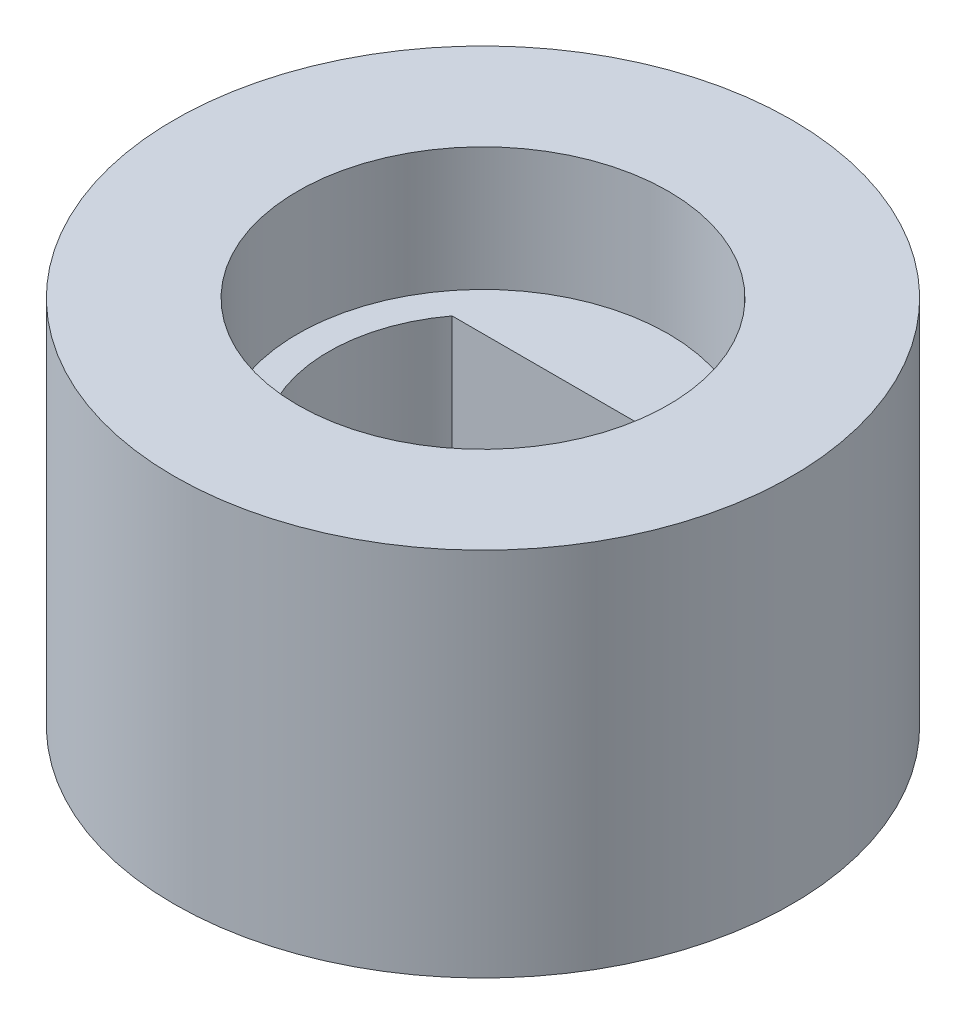
SolidWorks part; units mm, degrees
ref_plane "前视基准面" through (0, 0, 0) normal (0, 0, 1) x (1, 0, 0)
ref_plane "上视基准面" through (0, 0, 0) normal (0, 1, 0) x (1, 0, 0)
ref_plane "右视基准面" through (0, 0, 0) normal (1, 0, 0) x (0, 0, -1)
sketch "草图1" plane through (0, 0, 0) normal (0, 1, 0) x (1, 0, 0)
  line L0 (-2, 1.5) -> (2, 1.5)
  arc A0 (-2, 1.5) -> (2, 1.5) centre (0, 0) ccw
  circle A1 centre (0, 0) radius 5
  circle A2 centre (0, 0) radius 3
  dimension "D1" = 5
  dimension "D2" = 6
  dimension "D3" = 10
  dimension "D4" = 1.5
extrude "凸台-拉伸1" add sketch "草图1" along normal blind 4 contours A1 A2 | A2 A0 L0 region at (-4.8586, 0, 0) region at (-2.9151, 0, 0)
extrude "凸台-拉伸2" add sketch "草图1<3>" along normal blind 2 from surface contours A1 A2 region at (-4.8586, 0, 0) starting at face at (0, 4, 5)
sketch "草图1<3>" plane through (0, 0, 0) normal (0, 1, 0) x (1, 0, 0) same geometry as "草图1"
